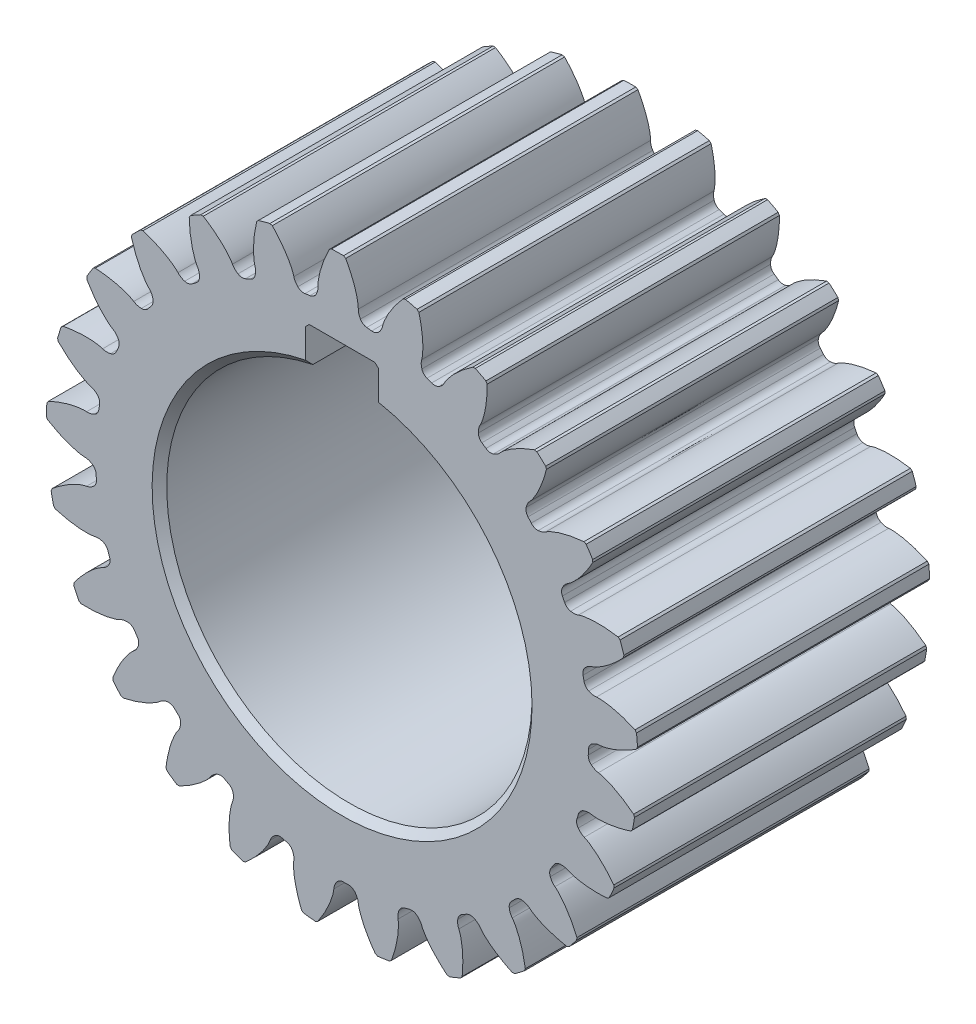
SolidWorks part; units mm, degrees
material "1.6587 (18CrNiMo7-6)"
ref_plane "Front Plane" through (0, 0, 0) normal (0, 0, 1) x (1, 0, 0)
ref_plane "Top Plane" through (0, 0, 0) normal (0, 1, 0) x (1, 0, 0)
ref_plane "Right Plane" through (0, 0, 0) normal (1, 0, 0) x (0, 0, -1)
sketch "Sketch1" plane through (0, 0, 0) normal (0, 0, 1) x (1, 0, 0)
  circle A0 centre (0, 0) radius 33.75
  dimension "D1" = 67.5
extrude "Boss-Extrude1" add sketch "Sketch1" along normal blind 40
sketch "Sketch2" plane through (0, 0, 40) normal (0, 0, 1) x (1, 0, 0)
  line L0 (0, 0) -> (0, 30) construction
  line L1 (5, 24.4949) -> (5, 30)
  line L2 (-5, 24.4949) -> (-5, 30)
  line L4 (5, 30) -> (-5, 30)
  line L5 (5, 0) -> (5, 30) construction
  line L6 (-5, 0) -> (-5, 30) construction
  arc A0 (-5, 24.4949) -> (5, 24.4949) centre (0, 0) ccw
  dimension "D1" = 50
  dimension "D2" = 30
  dimension "D3" = 5
  dimension "D4" = 5
extrude "Cut-Extrude1" cut sketch "Sketch2" against normal blind 40
sketch "Sketch3" plane through (0, 0, 0) normal (0, 0, 1) x (1, 0, 0)
  line L0 (0, 0) -> (37.4956, 0.5729) construction
  line L1 (0, 0) -> (48.4691, 3.7936) construction
  arc A0 (33.7263, -1.2647) -> (33.1188, 6.4967) centre (0, 0) ccw
  circle A1 centre (0, 0) radius 37.5 construction
  arc A2 (40.4431, 2.1452) -> (40.2844, 4.1733) centre (0, 0) ccw
  arc A5 (33.7556, 5.683) -> (33.1188, 6.4967) centre (34.2375, 6.7161) cw
  arc A6 (34.2287, -0.3619) -> (33.7263, -1.2647) centre (34.8655, -1.3075) ccw
  spline S0 degree 4 poles (35.2458, -0.0082) (35.2551, -0.0079) (35.2814, -0.0069) (35.3311, -0.0034) (35.412, 0.0044) (35.515, 0.0173) (35.6478, 0.0375) (35.804, 0.0657) (35.9751, 0.1015) (36.1608, 0.1454) (36.3455, 0.1937) (36.5292, 0.2459) (36.7117, 0.3018) (36.9321, 0.3737) (37.1955, 0.4662) (37.5018, 0.5831) (37.8473, 0.7261) (38.1972, 0.8829) (38.5397, 1.0464) (38.8834, 1.2219) (39.2142, 1.3992) (39.5553, 1.5939) (39.8688, 1.779) (40.217, 1.998) (40.4971, 2.1782) (40.8631, 2.4281) (41.0783, 2.5794) (41.3288, 2.7607) (41.4394, 2.8435) (41.5075, 2.8944) knots 0 0 0 0 0 0.005377 0.015084 0.028532 0.04661 0.064855 0.092111 0.119476 0.146842 0.174209 0.201575 0.228941 0.256307 0.307035 0.361767 0.4165 0.471232 0.525964 0.580697 0.635429 0.690161 0.744894 0.799626 0.854358 0.909091 0.954545 1 1 1 1 1 construction
  spline S1 degree 4 poles (35.2458, -0.0082) (35.2551, -0.0079) (35.2814, -0.0069) (35.3311, -0.0034) (35.412, 0.0044) (35.515, 0.0173) (35.6478, 0.0375) (35.804, 0.0657) (35.9751, 0.1015) (36.1608, 0.1454) (36.3455, 0.1937) (36.5292, 0.2459) (36.7117, 0.3018) (36.9321, 0.3737) (37.1955, 0.4662) (37.5018, 0.5831) (37.8473, 0.7261) (38.1972, 0.8829) (38.5397, 1.0464) (38.8834, 1.2219) (39.2142, 1.3992) (39.5553, 1.5939) (39.8688, 1.779) (40.1535, 1.9581) (40.322, 2.0657) (40.4216, 2.131) (40.4431, 2.1452) knots 0 0 0 0 0 0.005377 0.015084 0.028532 0.04661 0.064855 0.092111 0.119476 0.146842 0.174209 0.201575 0.228941 0.256307 0.307035 0.361767 0.4165 0.471232 0.525964 0.580697 0.635429 0.690161 0.744894 0.799626 0.814456 0.814456 0.814456 0.814456 0.814456
  spline S2 degree 2 poles (35.2458, -0.0082) (34.7334, -0.022) (34.2287, -0.3619) knots 0 0 0 1 1 1
  spline S3 degree 2 poles (34.8153, 5.4918) (34.307, 5.4257) (33.7556, 5.683) knots 0 0 0 1 1 1
  spline S4 degree 4 poles (34.8153, 5.4918) (34.8246, 5.493) (34.8507, 5.4961) (34.9003, 5.5003) (34.9815, 5.5053) (35.0852, 5.5085) (35.2196, 5.5092) (35.3782, 5.5056) (35.5528, 5.497) (35.7431, 5.4825) (35.933, 5.4635) (36.1226, 5.4405) (36.3116, 5.4137) (36.5406, 5.3769) (36.8151, 5.3266) (37.1358, 5.2588) (37.4994, 5.1712) (37.8695, 5.0707) (38.2332, 4.9626) (38.6, 4.8426) (38.9544, 4.719) (39.3216, 4.5798) (39.6601, 4.4457) (39.9692, 4.3131) (40.1523, 4.2329) (40.2609, 4.184) (40.2844, 4.1733) knots 0 0 0 0 0 0.005377 0.015084 0.028532 0.04661 0.064855 0.092111 0.119476 0.146842 0.174209 0.201575 0.228941 0.256307 0.307035 0.361767 0.4165 0.471232 0.525964 0.580697 0.635429 0.690161 0.744894 0.799626 0.814456 0.814456 0.814456 0.814456 0.814456
  point P1 (34.8655, -1.3075)
  dimension "D1" = 75
  dimension "D2" = 67.5
  dimension "D3" = 81
  dimension "D4" = 2.28
  dimension "D5" = 3.6
extrude "Boss-Extrude2" add sketch "Sketch3" along normal blind 40
chamfer "Chamfer3" distance 0.5 2 edges at (5, 30, 20) (-5, 30, 20)
chamfer "Chamfer4" distance 1.8 1 edges at (0, -25, 0)
chamfer "Chamfer5" distance 1 1 edges at (0, -25, 40)
chamfer "Chamfer6" distance 0.2 2 edges at (40.4431, 2.1452, 20) (40.2844, 4.1733, 20)
pattern_circular "CirPattern1" count 25 over 360 about axis through (0, 0, 40) along (0, 0, -1) of "Chamfer6", "Boss-Extrude2"
